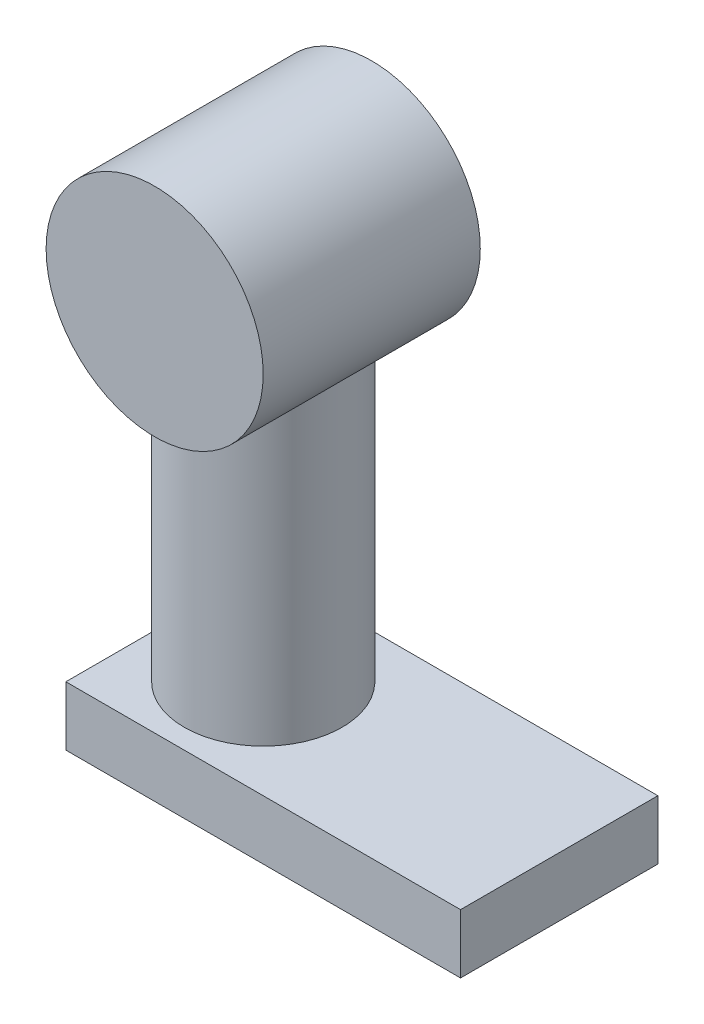
SolidWorks part; units mm, degrees
ref_plane "Front Plane" through (0, 0, 0) normal (0, 0, 1) x (1, 0, 0)
ref_plane "Top Plane" through (0, 0, 0) normal (0, 1, 0) x (1, 0, 0)
ref_plane "Right Plane" through (0, 0, 0) normal (1, 0, 0) x (0, 0, -1)
sketch "Sketch1" plane through (0, 0, 0) normal (0, 1, 0) x (1, 0, 0)
  circle A0 centre (0, 0) radius 40
  dimension "D1" = 80
extrude "Boss-Extrude1" add sketch "Sketch1" along normal blind 190
sketch "Sketch2" plane through (0, 0, 0) normal (0, 0, 1) x (1, 0, 0)
  line L0 (40, 190) -> (-40, 190) construction
  circle A0 centre (0, 190) radius 55
  dimension "D1" = 110
extrude "Boss-Extrude2" add sketch "Sketch2" along normal mid plane 110
sketch "Sketch3" plane through (0, 0, 0) normal (0, -1, 0) x (1, 0, 0)
  line L0 (0, 0) -> (155.8534, 0) construction
  line L1 (-50, 50) -> (150, 50)
  line L2 (-50, 50) -> (-50, -50)
  line L3 (-50, -50) -> (150, -50)
  line L4 (150, 50) -> (150, -50)
  dimension "D1" = 50
  dimension "D2" = 200
  dimension "100" = 100
extrude "Boss-Extrude3" add sketch "Sketch3" along normal blind 30
ref_axis "Axis1" through (0, 190, 55) along (0, 0, -1)
